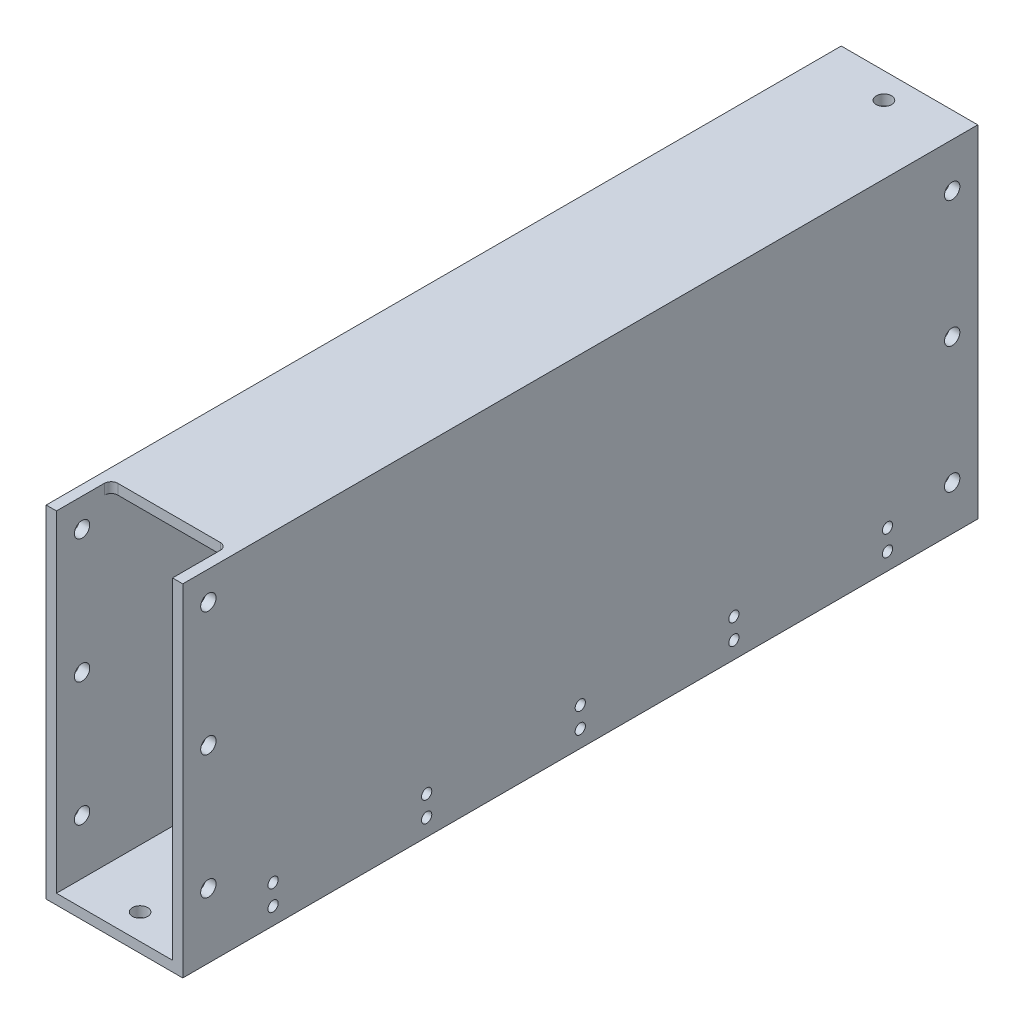
SolidWorks part; units mm, degrees
note: '?' marks a value the reader was unsure of.
material "3.3547 (EN-AW 5083)"
ref_plane "Front Plane" through (0, 0, 0) normal (0, 0, 1) x (1, 0, 0)
ref_plane "Top Plane" through (0, 0, 0) normal (0, 1, 0) x (1, 0, 0)
ref_plane "Right Plane" through (0, 0, 0) normal (1, 0, 0) x (0, 0, -1)
ref_axis "Axis1" through (0, 0, 272.0798) along (0, 0, -1)?
ref_plane "Plane1" through (0, 0, 30) normal (0, 0, 1) x (1, 0, 0)
ref_axis "Wrist" through (0, -55.814, 287.9) along (0, 1, 0)?
ref_plane "Plane2" through (0, 0, 287.9) normal (0, 0, 1) x (1, 0, 0)
ref_plane "Plane3" through (0, 0, 262.9) normal (0, 0, 1) x (1, 0, 0)
ref_point "Point2"
sketch "Sketch1" plane through (0, 0, 30) normal (0, 0, 1) x (1, 0, 0)
  line L0 (-20, 50) -> (20, 50) construction
  line L1 (-20, -50) -> (20, -50)
  line L2 (-20, -50) -> (-20, 50)
  line L3 (-20, 50) -> (20, 50)
  line L4 (20, -50) -> (20, 50)
  line L5 (-20, -50) -> (20, 50) construction
  line L6 (-20, 50) -> (20, -50) construction
  line L7 (-20, -50) -> (-20, 50) construction
  line L8 (-17, -47) -> (-17, 47)
  line L9 (-17, 47) -> (17, 47)
  line L10 (17, -47) -> (17, 47)
  line L11 (-17, -47) -> (17, -47)
  circle A0 centre (0, 0) radius 53.8516 construction
  point P0 (0, 0)
  dimension "D2" = 107.7033
  dimension "D1" = 3
extrude "Boss-Extrude1" add sketch "Sketch1" along normal up to vertex (232.9 mm away)
sketch "Sketch7" plane through (0, 50, 0) normal (0, 1, 0) x (1, 0, 0)
  line L4 (17, -30) -> (-17, -30) construction
  line L5 (17, -30) -> (-17, -30)
  arc A0 (-17, -30) -> (17, -30) centre (0, 0) ccw
extrude "Cut-Extrude1" [suppressed] cut sketch "Sketch7" against normal up to next
sketch "Sketch8" plane through (0, 50, 0) normal (0, 1, 0) x (1, 0, 0)
  line L0 (17, -262.9) -> (-17, -262.9) construction
  line L1 (17, -262.9) -> (-17, -262.9)
  line L2 (-17, -262.9) -> (-17, -246.9)
  line L3 (-17, -246.9) -> (17, -246.9)
  line L4 (17, -246.9) -> (17, -262.9)
  line L5 (-16, -247.9) -> (16, -247.9) construction
  line L6 (-16, -247.9) -> (16, -247.9) construction
  dimension "D1" = 1
extrude "Cut-Extrude2" cut sketch "Sketch8" against normal up to next and the other way through all
hole_wizard "M4 Clearance Hole1" positions "3DSketch1" profile "Sketch9" hole size "M4" standard "DIN" end condition up to next
sketch3d "3DSketch1"
  circle A0 centre (17, -37, 37.5) radius 1.65 construction
  circle A1 centre (17, 0, 37.5) radius 1.65 construction
  circle A2 centre (17, 37, 37.5) radius 1.65 construction
  circle A3 centre (0, 47, 37.5) radius 1.65 construction
  circle A4 centre (-17, 37, 37.5) radius 1.65 construction
  circle A5 centre (-17, 0, 37.5) radius 1.65 construction
  circle A6 centre (-17, -37, 37.5) radius 1.65 construction
  circle A7 centre (0, -47, 37.5) radius 1.65 construction
  circle A8 centre (0, -47, 255.4) radius 2.15 construction
  circle A9 centre (-17, -31, 255.4) radius 1.65 construction
  circle A10 centre (-17, 5.3, 255.4) radius 1.65 construction
  circle A11 centre (-17, 41.6, 255.4) radius 1.65 construction
  circle A12 centre (17, 41.6, 255.4) radius 1.65 construction
  circle A13 centre (17, 5.3, 255.4) radius 1.65 construction
  circle A14 centre (17, -31, 255.4) radius 1.65 construction
  point P0 (20, 37, 37.5)
  point P2 (20, 0, 37.5)
  point P9 (0, 50, 37.5)
  point P11 (-20, -37, 37.5)
  point P13 (-20, 0, 37.5)
  point P15 (-20, 37, 37.5)
  point P17 (0, -50, 37.5)
  point P19 (0, -50, 255.4)
  point P21 (-20, -31, 255.4)
  point P23 (-20, 5.3, 255.4)
  point P25 (-20, 41.6, 255.4)
  point P27 (20, -31, 255.4)
  point P29 (20, 5.3, 255.4)
  point P31 (20, 41.6, 255.4)
  point P35 (20, -37, 37.5)
  point P40 (18.65, -37, 37.5)
  point P43 (18.65, 0, 37.5)
  point P46 (18.65, 37, 37.5)
  point P50 (0, 48.65, 37.5)
  point P53 (-18.65, 37, 37.5)
  point P57 (-18.65, 0, 37.5)
  point P61 (-18.65, -37, 37.5)
  point P65 (0, -48.65, 37.5)
  point P68 (0, -44.85, 255.4)
  point P72 (-18.65, -31, 255.4)
  point P76 (-18.65, 5.3, 255.4)
  point P80 (-18.65, 41.6, 255.4)
  point P84 (18.65, 41.6, 255.4)
  point P88 (18.65, 5.3, 255.4)
  point P92 (18.65, -31, 255.4)
sketch "Sketch9" plane through (20, 37, 37.5) normal (0, 1, 0) x (0, 0, -1)
  line L0 (0, 0) -> (0, 3)
  line L1 (0, 3) -> (2.25, 3)
  line L2 (2.25, 3) -> (2.25, 0)
  line L5 (2.25, 0) -> (0, 0)
  line L11 (0, -6.35) -> (0, 107.95) construction
  dimension "Thru Hole Dia." = 4.5
  dimension "Thru Hole Depth" = 3
fillet "Fillet1" radius 2 2 edges at (17, 48.5, 246.9) (-17, 48.5, 246.9)
sketch "Sketch10" plane through (0, 0, 0) normal (1, 0, 0) x (0, 0, -1)
  line L0 (-30, -50) -> (-30, 50) construction
  line L1 (-262.9, -50) -> (-262.9, 50) construction
  line L2 (-30, -50) -> (-30, 50) construction
  line L3 (-262.9, -50) -> (-262.9, 50) construction
  line L4 (-262.9, 0) -> (-30, 0) construction
  line L5 (-272.0798, 0) -> (-17.0838, 0) construction
  circle A0 centre (-196, 0) radius 30
  circle A1 centre (-138, 0) radius 20
  circle A2 centre (-95, 0) radius 15
  point P14 (-158, 0)
  point P17 (-166, 0)
  point P18 (-118, 0)
  point P19 (-110, 0)
  point P20 (-80, 0)
  dimension "D1" = 8
  dimension "D4" = 60
  dimension "D5" = 40
  dimension "D6" = 30
  dimension "D2" = 8
  dimension "D3" = 50
extrude "Cut-Extrude3" [suppressed] cut sketch "Sketch10" against normal through all both and the other way through all
sketch "Sketch13" plane through (20, 0, 0) normal (1, 0, 0) x (0, 0, -1)
  line L0 (-262.9, -47) -> (-30, -47) construction
  line L1 (-262.9, -47) -> (-30, -47) construction
  line L2 (-262.9, -42) -> (-30, -42) construction
  line L3 (-236.45, -39) -> (-236.45, -45) construction
  line L4 (-262.9, -50) -> (-262.9, 50) construction
  line L5 (-191.45, -39) -> (-191.45, -45) construction
  line L6 (-146.45, -39) -> (-146.45, -45) construction
  line L7 (-101.45, -39) -> (-101.45, -45) construction
  line L8 (-56.45, -39) -> (-56.45, -45) construction
  line L9 (-236.45, -39) -> (-191.45, -39) construction
  point P8 (-236.45, -42)
  point P10 (-236.45, -39)
  point P12 (-236.45, -45)
  point P37 (-191.45, -39)
  point P39 (-146.45, -39)
  point P41 (-101.45, -39)
  point P43 (-56.45, -39)
  point P45 (-191.45, -45)
  point P47 (-146.45, -45)
  point P49 (-101.45, -45)
  point P51 (-56.45, -45)
  dimension "D1" = 5
  dimension "D2" = 6
  dimension "D3" = 26.45
  dimension "D4" = 5
  dimension "D5" = 45
hole_wizard "Ø3.0 (3) Diameter Hole1" positions "Sketch13" profile "Sketch12" hole size "Ø3.0" standard "DIN"
sketch "Sketch12" plane through (20, -45, 56.45) normal (0, 1, 0) x (0, 0, -1)
  line L0 (0, 0) -> (0, 3)
  line L1 (0, 3) -> (1.5, 3)
  line L2 (1.5, 3) -> (1.5, 0)
  line L5 (1.5, 0) -> (0, 0)
  line L11 (0, -6.35) -> (0, 107.95) construction
  dimension "Thru Hole Dia." = 3
  dimension "Thru Hole Depth" = 3
